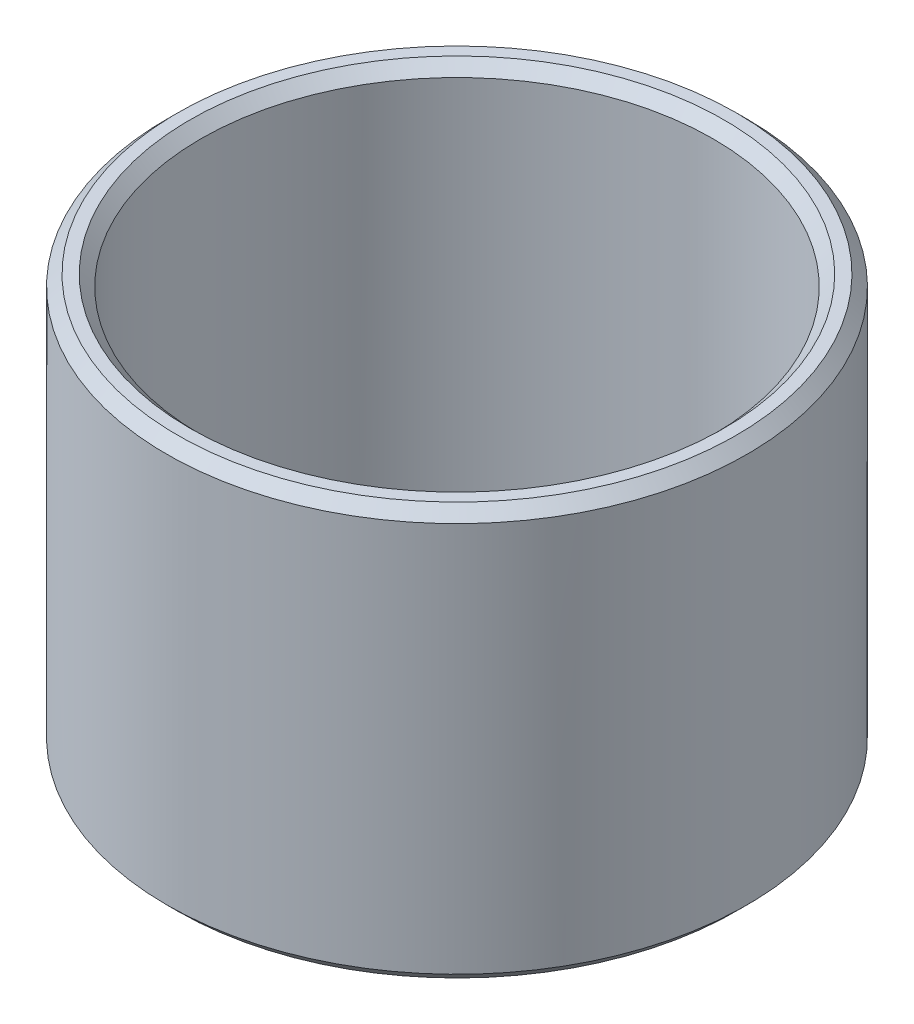
SolidWorks part; units mm, degrees
ref_plane "Front Plane" through (0, 0, 0) normal (0, 0, 1) x (1, 0, 0)
ref_plane "Top Plane" through (0, 0, 0) normal (0, 1, 0) x (1, 0, 0)
ref_plane "Right Plane" through (0, 0, 0) normal (1, 0, 0) x (0, 0, -1)
sketch "Sketch1" plane through (0, 0, 0) normal (0, 1, 0) x (1, 0, 0)
  circle A0 centre (0, 0) radius 50
  dimension "SLEEVE_OD" = 100
extrude "Boss-Extrude1" add sketch "Sketch1" along normal blind 70.9985
sketch "Sketch2" plane through (0, 0, 0) normal (0, 1, 0) x (1, 0, 0)
  circle A0 centre (0, 0) radius 44.1306
  dimension "BORE_D" = 88.2612
extrude "Cut-Extrude1" cut sketch "Sketch2" along normal through all
chamfer "Chamfer1" distance 1.8848 angle 45 4 edges at (0, 70.9985, 44.1306) (0, 0, 44.1306) (0, 0, 50) (0, 70.9985, 50)
